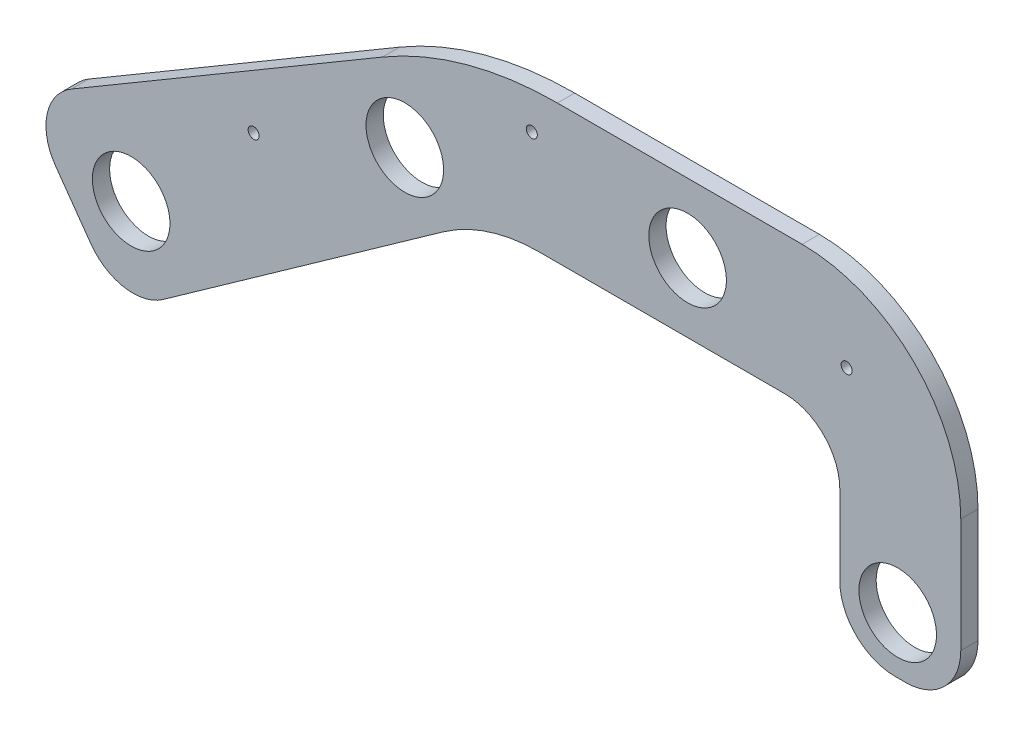
SolidWorks part; units mm, degrees
ref_plane "Front Plane" through (0, 0, 0) normal (0, 0, 1) x (1, 0, 0)
ref_plane "Top Plane" through (0, 0, 0) normal (0, 1, 0) x (1, 0, 0)
ref_plane "Right Plane" through (0, 0, 0) normal (1, 0, 0) x (0, 0, -1)
sketch "Sketch1" plane through (0, 0, 0) normal (0, 0, 1) x (1, 0, 0)
  line L1 (0, 0) -> (-134.6806, -95.4942)
  line L2 (174.7261, -31.75) -> (174.7261, 50.8695)
  line L3 (174.7261, 50.8695) -> (-8.4603, 50.8695)
  line L4 (-134.6806, -95.4942) -> (-170.6999, -44.6942)
  line L5 (-170.6999, -44.6942) -> (-8.4603, 50.8695)
  line L6 (130.175, 0) -> (130.175, -69.85)
  line L7 (130.175, -69.85) -> (174.7261, -69.85)
  line L8 (174.7261, -69.85) -> (174.7261, -31.75)
  line L9 (0, 0) -> (130.175, 0)
  dimension "D1" = 69.85
  dimension "D2" = 130.175
extrude "Boss-Extrude1" add sketch "Sketch1" along normal blind 3.175
fillet "Fillet4" radius 127 1 edges at (-8.4603, 50.8695, 1.5875)
fillet "Fillet8" radius 6.35 1 edges at (174.7261, 50.8695, 1.5875)
sketch "Sketch4" plane through (0, 0, 0) normal (0, 0, -1) x (-1, 0, 0)
  circle A0 centre (-151.5033, -49.0245) radius 14.2875
  circle A1 centre (130.8438, -58.9847) radius 14.2875
  circle A2 centre (30.055, 8.563) radius 14.2875
  circle A4 centre (-74.1124, 25.4) radius 14.2875
  circle A5 centre (85.7284, -14.6121) radius 2.032
  circle A6 centre (-132.6776, 19.6768) radius 2.032
  circle A7 centre (-16.7303, 36.918) radius 2.032
  dimension "D1" = 28.575
  dimension "D2" = 28.575
  dimension "D3" = 28.575
  dimension "D4" = 4.064
  dimension "D5" = 28.575
  dimension "D6" = 4.064
  dimension "D7" = 4.064
extrude "Cut-Extrude1" cut sketch "Sketch4" against normal blind 18.415
fillet "Fillet20" radius 33.02 1 edges at (-134.6806, -95.4942, 1.5875)
extrude "Boss-Extrude3" add sketch "Sketch1<3>" along normal blind 6.35
sketch "Sketch1<3>" plane through (0, 0, 0) normal (0, 0, 1) x (1, 0, 0) same geometry as "Sketch1"
fillet "Fillet23" radius 127 1 edges at (-8.4603, 50.8695, 3.175)
fillet "Fillet24" radius 19.05 1 edges at (-170.6999, -44.6942, 3.175)
fillet "Fillet25" radius 19.05 1 edges at (-134.6806, -95.4942, 3.175)
extrude "Cut-Extrude2" cut sketch "Sketch4<2>" against normal blind 6.35
sketch "Sketch4<2>" plane through (0, 0, 0) normal (0, 0, -1) x (-1, 0, 0) same geometry as "Sketch4"
fillet "Fillet27" radius 60.96 1 edges at (0, 0, 3.175)
fillet "Fillet28" radius 20.32 1 edges at (130.175, 0, 3.175)
fillet "Fillet29" radius 20.32 1 edges at (130.175, -69.85, 3.175)
fillet "Fillet30" radius 20.32 1 edges at (174.7261, -69.85, 3.175)
fillet "Fillet31" radius 58.42 1 edges at (174.7261, 50.8695, 3.175)
